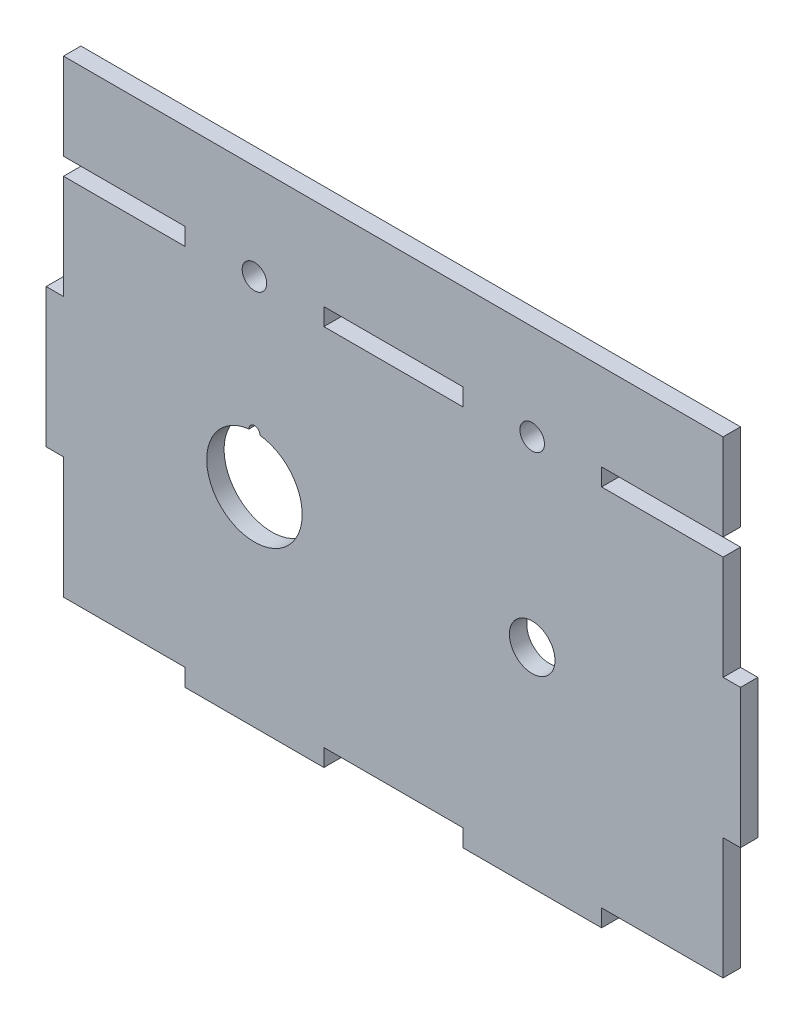
SolidWorks part; units mm, degrees
ref_plane "Front Plane" through (0, 0, 0) normal (0, 0, 1) x (1, 0, 0)
ref_plane "Top Plane" through (0, 0, 0) normal (0, 1, 0) x (1, 0, 0)
ref_plane "Right Plane" through (0, 0, 0) normal (1, 0, 0) x (0, 0, -1)
sketch "Sketch1" plane through (0, 0, 0) normal (0, 0, 1) x (1, 0, 0)
  line L1 (0, 0) -> (127, 0)
  line L2 (0, 0) -> (0, 88.9)
  line L3 (0, 88.9) -> (127, 88.9)
  line L4 (127, 0) -> (127, 88.9)
  dimension "D1" = 127
  dimension "D2" = 88.9
extrude "Boss-Extrude1" add sketch "Sketch1" along normal blind 3.175
sketch "Sketch5" plane through (0, 0, 3.175) normal (0, 0, 1) x (1, 0, 0)
  line L1 (0, 0) -> (3.175, 0)
  line L2 (0, 0) -> (0, 25.4)
  line L3 (0, 25.4) -> (3.175, 25.4)
  line L4 (3.175, 0) -> (3.175, 25.4)
  dimension "D1" = 25.4
  dimension "D2" = 3.175
extrude "Cut-Extrude4" cut sketch "Sketch5" against normal blind 6.35
sketch "Sketch6" plane through (0, 0, 3.175) normal (0, 0, 1) x (1, 0, 0)
  line L1 (0, 0) -> (25.4, 0)
  line L2 (0, 0) -> (0, 3.175)
  line L3 (0, 3.175) -> (25.4, 3.175)
  line L4 (25.4, 0) -> (25.4, 3.175)
  dimension "D1" = 3.175
  dimension "D2" = 25.4
extrude "Cut-Extrude5" cut sketch "Sketch6" against normal blind 6.35
pattern_linear "LPattern5" count 2 spacing 50.8 along (0, 1, 0) count 2 spacing 123.825 along (1, 0, 0) of "Cut-Extrude4"
pattern_linear "LPattern6" count 3 spacing 50.8 along (1, 0, 0) count 2 spacing 69.85 along (0, 1, 0) of "Cut-Extrude5"
hole_wizard "#8 Clearance Hole1" positions "Sketch10" profile "Sketch9" hole size "#8" standard "ANSI Inch"
sketch "Sketch10" plane through (0, 0, 3.175) normal (0, 0, 1) x (1, 0, 0)
  line L2 (25.4, 69.85) -> (25.4, 73.025) construction
  line L3 (76.2, 73.025) -> (50.8, 73.025) construction
  line L4 (76.2, 69.85) -> (76.2, 73.025) construction
  point P0 (38.1, 71.4375)
  point P2 (88.9, 71.4375)
  point P10 (25.4, 71.4375)
  dimension "D1" = 12.7
  dimension "D3" = 12.7
  dimension "D4" = 1.5875
sketch "Sketch9" plane through (38.1, 71.4375, 3.175) normal (1, 0, 0) x (0, -1, 0)
  line L0 (0, 0) -> (0, 11.5107)
  line L1 (0, 11.5107) -> (2.2479, 10.16)
  line L2 (2.2479, 10.16) -> (2.2479, 0)
  line L5 (2.2479, 0) -> (0, 0)
  line L10 (0, 11.5107) -> (-2.2479, 10.16) construction
  line L11 (0, -6.35) -> (0, 107.95) construction
  dimension "Hole Dia." = 4.4958
  dimension "Hole Depth" = 10.16
  dimension "Drill Angle" = 118
sketch "Sketch11" plane through (0, 0, 3.175) normal (0, 0, 1) x (1, 0, 0)
  line L1 (0, 88.9) -> (3.175, 88.9)
  line L2 (0, 88.9) -> (0, 76.2)
  line L3 (0, 76.2) -> (3.175, 76.2)
  line L4 (3.175, 88.9) -> (3.175, 76.2)
  line L5 (127, 88.9) -> (123.825, 88.9)
  line L6 (127, 88.9) -> (127, 76.2)
  line L7 (127, 76.2) -> (123.825, 76.2)
  line L8 (123.825, 88.9) -> (123.825, 76.2)
extrude "Cut-Extrude6" cut sketch "Sketch11" against normal blind 7.62
sketch "Sketch12" plane through (0, 0, 3.175) normal (0, 0, 1) x (1, 0, 0)
  line L0 (0, 50.8) -> (0, 25.4) construction
  line L1 (123.825, 88.9) -> (3.175, 88.9) construction
  circle A0 centre (38.1, 38.1) radius 8.7312
  circle A1 centre (38.1, 46.8312) radius 1
  dimension "D1" = 17.4625
  dimension "D2" = 2
  dimension "D3" = 38.1
  dimension "D4" = 50.8
extrude "Cut-Extrude7" cut sketch "Sketch12" against normal blind 7.62 contours A1 A0 | A0 A1 | A0 A1 region at (38.1, 38.0466, 3.175) region at (38.1, 46.3967, 3.175) region at (38.1, 47.2452, 3.175)
sketch "Sketch13" plane through (0, 0, 3.175) normal (0, 0, 1) x (1, 0, 0)
  line L0 (127, 25.4) -> (127, 50.8) construction
  line L1 (123.825, 88.9) -> (3.175, 88.9) construction
  circle A0 centre (88.9, 38.1) radius 4.1672
  dimension "D1" = 8.3344
  dimension "D2" = 38.1
  dimension "D3" = 50.8
extrude "Cut-Extrude8" cut sketch "Sketch13" against normal blind 7.62
